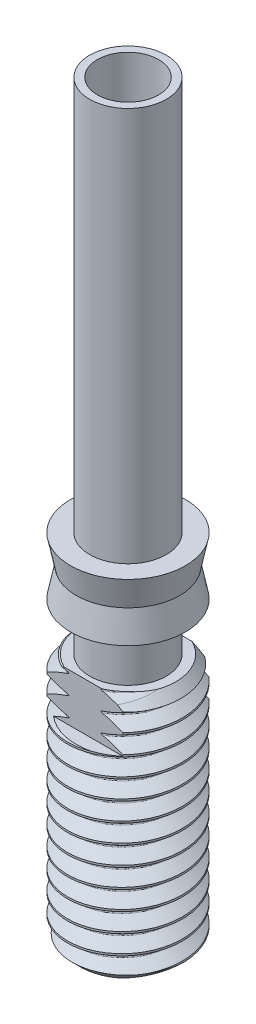
SolidWorks part; units mm, degrees
material "Plain Carbon Steel"
ref_plane "Front Plane" through (0, 0, 0) normal (0, 0, 1) x (1, 0, 0)
ref_plane "Top Plane" through (0, 0, 0) normal (0, 1, 0) x (1, 0, 0)
ref_plane "Right Plane" through (0, 0, 0) normal (1, 0, 0) x (0, 0, -1)
sketch "Sketch1" plane through (0, 0, 0) normal (0, 0, 1) x (1, 0, 0)
  line L0 (0, 0) -> (0, 49.7104) construction
  line L1 (1.6, 0) -> (2.5, 0)
  line L2 (3, 0.5) -> (3, 12.4)
  line L3 (2.5, 12.9) -> (2, 12.9)
  line L4 (2, 12.9) -> (2, 15.4)
  line L5 (2, 15.4) -> (3, 15.4)
  line L6 (3, 15.4) -> (2.7, 16.9)
  line L7 (2.7, 16.9) -> (3, 18.4)
  line L8 (3, 18.4) -> (2, 18.4)
  line L9 (2, 18.4) -> (2, 39)
  line L10 (2, 39) -> (1.6, 39)
  line L11 (1.6, 39) -> (1.6, 0)
  line L12 (3, 12.4) -> (2.5, 12.9)
  line L13 (2.5, 0) -> (3, 0.5)
  point P4 (3, 0)
  point P5 (3, 12.9)
  dimension "D1" = 3.2
  dimension "D2" = 4
  dimension "D3" = 39
  dimension "D4" = 6
  dimension "D5" = 6
  dimension "D6" = 3
  dimension "D7" = 0.3
  dimension "D8" = 2.5
  dimension "D9" = 12.9
revolve "Revolve1" add sketch "Sketch1" angle 360 about L0
sketch "Sketch2" plane through (0, 0, 0) normal (0, -1, 0) x (1, 0, 0)
  circle A0 centre (0, 0) radius 3 construction
  circle A1 centre (0, 0) radius 3
curve "Helix/Spiral1" pitch 1 height 13.5 radius 3 centre (0, 0, 0) axis (0, 1, 0) start towards (0, 0, -1)
ref_plane "Plane1" through (-3, 0, 0) normal (0, 0.053, 0.9986) x (1, 0, 0)
sketch "Sketch3" plane through (-3, 0, 0) normal (0, 0.053, 0.9986) x (1, 0, 0)
  line L0 (0, 0) -> (0, -0.9)
  line L1 (0, -0.9) -> (0.5789, -0.4908)
  line L2 (0.5789, -0.4092) -> (0, 0)
  line L3 (0, -0.45) -> (0.55, -0.45) construction
  arc A0 (0.5789, -0.4908) -> (0.5789, -0.4092) centre (0.55, -0.45) ccw
  dimension "D1" = 0.05
  dimension "D2" = 0.9
  dimension "D3" = 0.6
sweep "Cut-Sweep1" cut profiles "Sketch3" path "Helix/Spiral1"
sketch "Sketch4" plane through (0, 12.9, 0) normal (0, 1, 0) x (1, 0, 0)
  line L0 (-5.1188, 2.25) -> (5.1188, -2.25) construction
  line L1 (-5.1188, 2.25) -> (5.1188, 2.25)
  line L2 (-5.1188, 2.25) -> (-5.1188, -2.25)
  line L3 (-5.1188, -2.25) -> (5.1188, -2.25)
  line L4 (5.1188, 2.25) -> (5.1188, -2.25)
  dimension "D1" = 4.5
extrude "Cut-Extrude1" cut sketch "Sketch4" against normal blind 2.5 flip side to cut
